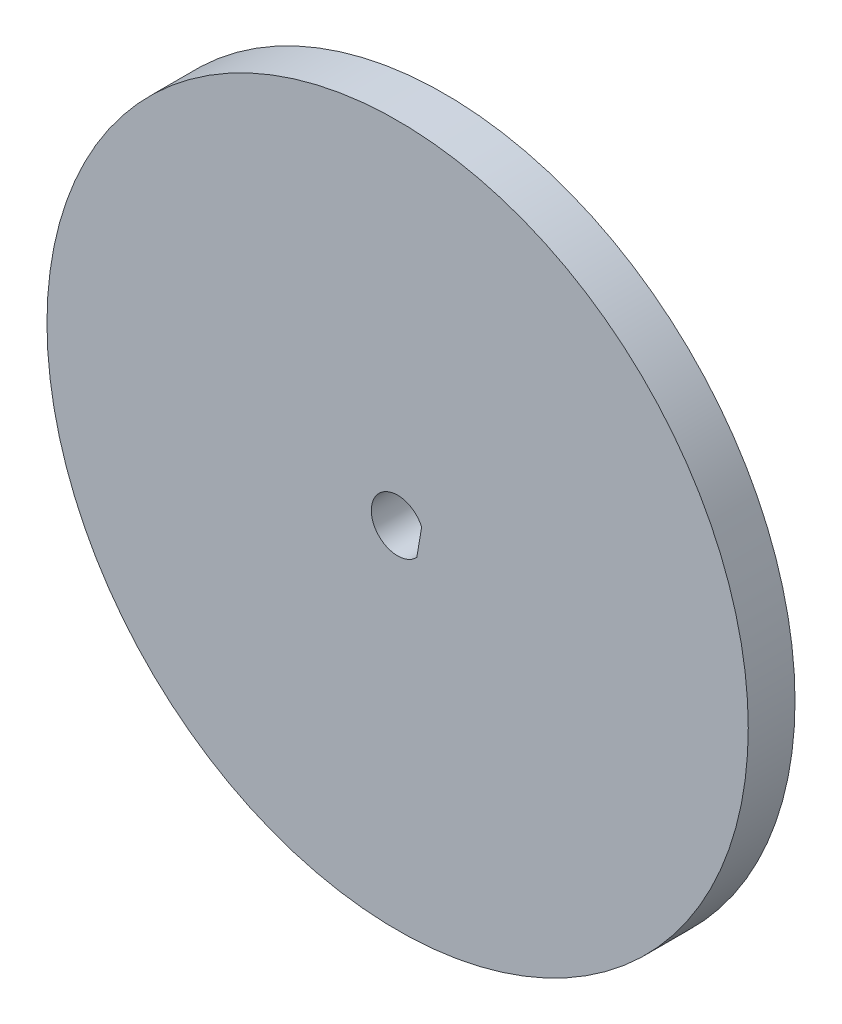
SolidWorks part; units mm, degrees
ref_plane "Front Plane" through (0, 0, 0) normal (0, 0, 1) x (1, 0, 0)
ref_plane "Top Plane" through (0, 0, 0) normal (0, 1, 0) x (1, 0, 0)
ref_plane "Right Plane" through (0, 0, 0) normal (1, 0, 0) x (0, 0, -1)
sketch "Sketch1" plane through (0, 0, 0) normal (0, 0, 1) x (1, 0, 0)
  circle A0 centre (-10.9917, 10.7964) radius 40
  dimension "D1" = 80
extrude "Boss-Extrude1" add sketch "Sketch1" along normal blind 5.334
sketch "Sketch3" plane through (0, 0, 5.334) normal (0, 0, 1) x (1, 0, 0)
  line L0 (-8.527, 10.3777) -> (-8.2493, 12.0126) construction
  line L1 (-8.8047, 8.7428) -> (-8.527, 10.3777) construction
  line L2 (-8.527, 10.3777) -> (-8.2493, 12.0126)
  line L3 (-8.8047, 8.7428) -> (-8.527, 10.3777)
  arc A0 (-8.2493, 12.0126) -> (-8.8047, 8.7428) centre (-10.9917, 10.7964) ccw construction
  arc A1 (-8.2493, 12.0126) -> (-8.8047, 8.7428) centre (-10.9917, 10.7964) ccw
extrude "Cut-Extrude1" cut sketch "Sketch3" against normal through all
equation "\"MDF\"= .21in"
equation "\"Foamcore\"= .13in"
equation "\"Gmaterial\"= \"MDF\""
equation "\"D1@Boss-Extrude1\"=\"MDF\""
